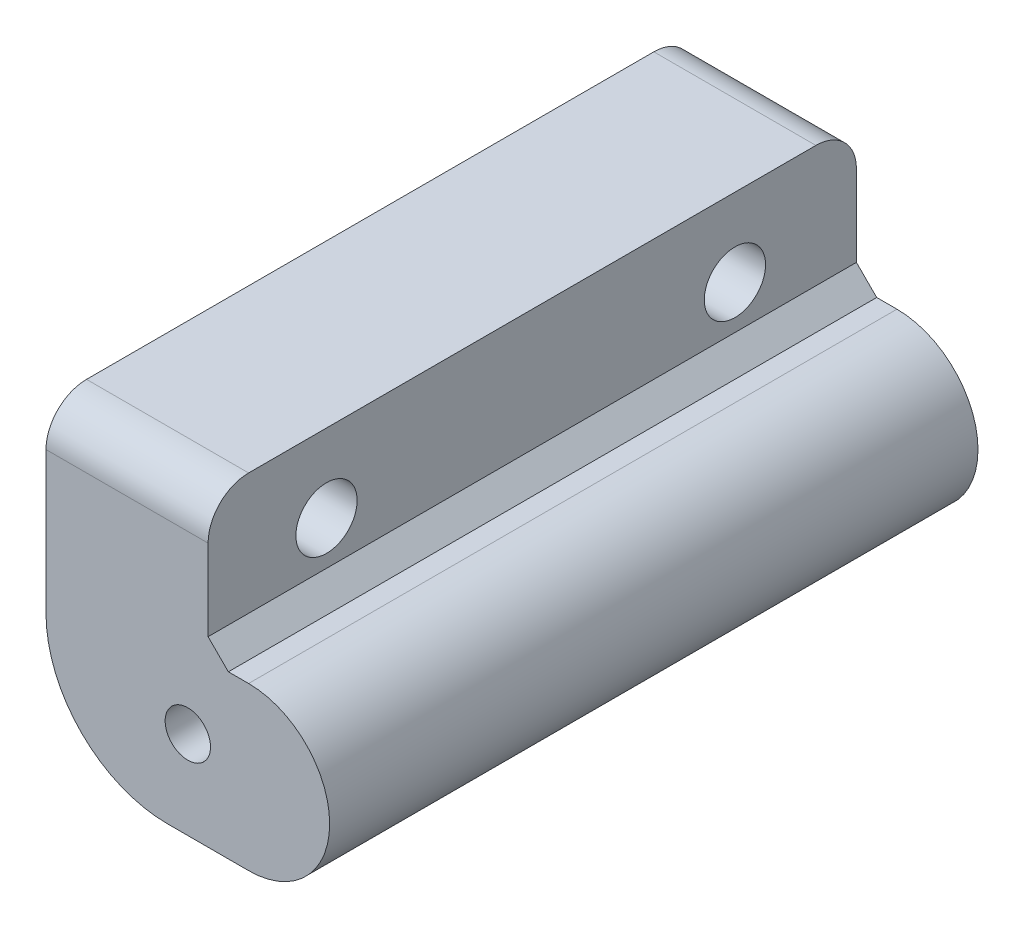
SolidWorks part; units mm, degrees
material "Polycarbonate"
ref_plane "Front Plane" through (0, 0, 0) normal (0, 0, 1) x (1, 0, 0)
ref_plane "Top Plane" through (0, 0, 0) normal (0, 1, 0) x (1, 0, 0)
ref_plane "Right Plane" through (0, 0, 0) normal (1, 0, 0) x (0, 0, -1)
sketch "Sketch1" plane through (0, 0, 0) normal (0, 0, 1) x (1, 0, 0)
  line L0 (0, 0) -> (0, 5.5562)
  line L1 (0, 5.5562) -> (-6.35, 5.5562)
  line L2 (-6.35, 5.5562) -> (-6.35, -6.35)
  line L3 (-6.35, -6.35) -> (4.7625, -6.35)
  line L4 (4.7625, -6.35) -> (4.7625, 0)
  line L5 (4.7625, 0) -> (0, 0)
  dimension "D1" = 6.35
  dimension "D2" = 4.7625
  dimension "D3" = 5.5562
  dimension "D4" = 6.35
extrude "Boss-Extrude1" add sketch "Sketch1" along normal blind 25.4
chamfer "Chamfer1" distance 0.7937 angle 45 1 edges at (0, 0, 12.7)
sketch "Sketch2" plane through (0, 0, 25.4) normal (0, 0, 1) x (1, 0, 0)
  line L0 (0, 0.7937) -> (0, 5.5562) construction
  line L2 (4.7625, 0) -> (0.7937, 0) construction
  circle A0 centre (-0.7937, -2.9032) radius 0.7938 construction
  circle A1 centre (-0.7937, -2.9032) radius 0.889
  dimension "D1" = 1.5875
  dimension "D3" = 1.778
  dimension "D2" = 2.9032
extrude "Cut-Extrude1" cut sketch "Sketch2" against normal through all
hole_wizard "M2 Clearance Hole1" positions "Sketch3" profile "Sketch4" hole size "M2" standard "ANSI Metric" end condition up to next
sketch "Sketch3" plane through (0, 0, 0) normal (1, 0, 0) x (0, 0, -1)
  line L1 (-25.4, 0.7937) -> (-25.4, 5.5562) construction
  line L2 (0, 0.7937) -> (0, 5.5562) construction
  line L3 (0, 0) -> (-25.4, 0) construction
  point P0 (-20.7609, 2.5)
  point P3 (-4.7609, 2.5)
  dimension "D1" = 2.5
  dimension "D2" = 4.6391
  dimension "D3" = 2.5
  dimension "D4" = 4.7609
sketch "Sketch4" plane through (0, 2.5, 20.7609) normal (0, 1, 0) x (0, 0, -1)
  line L0 (0, 0) -> (0, 6.35)
  line L1 (0, 6.35) -> (1.2, 6.35)
  line L2 (1.2, 6.35) -> (1.2, 0)
  line L5 (1.2, 0) -> (0, 0)
  line L11 (0, -6.35) -> (0, 107.95) construction
  dimension "Thru Hole Dia." = 2.4
  dimension "Thru Hole Depth" = 6.35
fillet "Fillet1" 2 edges at (4.7625, -6.35, 12.7) (4.7625, 0, 12.7) type full round first side face at (-0.7937, -6.35, 12.7) second side face at (2.7781, 0, 12.7) middle face at (4.7625, -3.175, 12.7)
fillet "Fillet2" radius 4.7625 1 edges at (-6.35, -6.35, 12.7)
fillet "Fillet3" radius 1.5875 2 edges at (-3.175, 5.5562, 0) (-3.175, 5.5562, 25.4)
